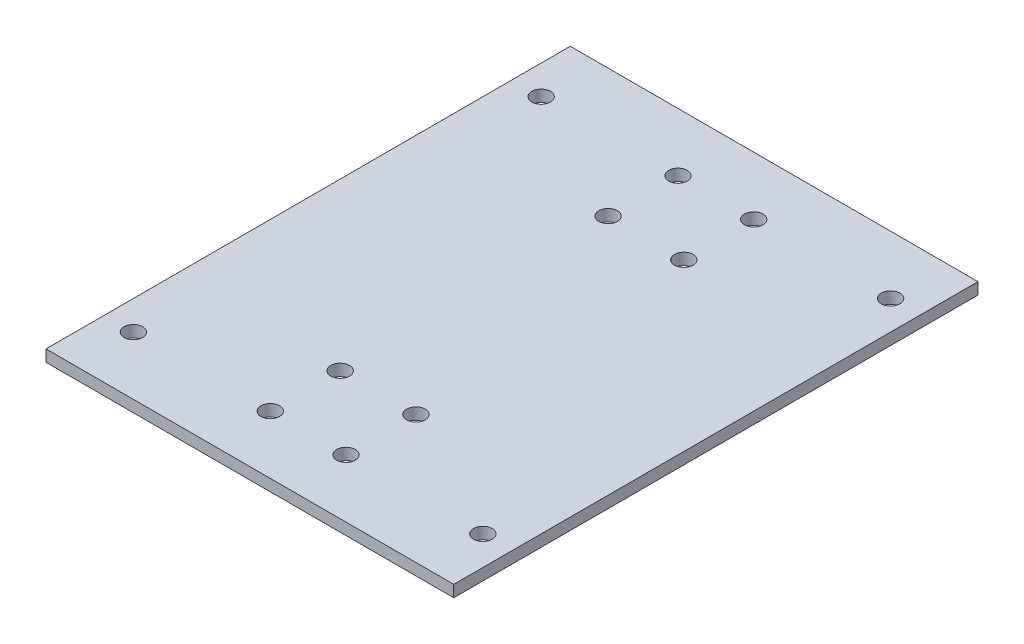
SolidWorks part; units mm, degrees
ref_plane "前基準面" through (0, 0, 0) normal (0, 0, 1) x (1, 0, 0)
ref_plane "上基準面" through (0, 0, 0) normal (0, 1, 0) x (1, 0, 0)
ref_plane "右基準面" through (0, 0, 0) normal (1, 0, 0) x (0, 0, -1)
sketch "草圖2" plane through (0, 0, 0) normal (0, 1, 0) x (1, 0, 0)
  line L1 (-35, -45) -> (35, -45)
  line L2 (-35, -45) -> (-35, 45)
  line L3 (-35, 45) -> (35, 45)
  line L4 (35, -45) -> (35, 45)
  line L5 (0, 45) -> (0, -45) construction
  line L6 (-35, 0) -> (35, 0) construction
  circle A0 centre (-6.5, 35) radius 1.6
  circle A1 centre (-6.5, -35) radius 1.6
  circle A2 centre (-6.5, 23) radius 1.6
  circle A3 centre (-6.5, -23) radius 1.6
  circle A4 centre (6.5, -35) radius 1.6
  circle A5 centre (6.5, -23) radius 1.6
  circle A6 centre (6.5, 23) radius 1.6
  circle A7 centre (6.5, 35) radius 1.6
  circle A8 centre (-30, 35) radius 1.6
  circle A9 centre (30, 35) radius 1.6
  circle A10 centre (-30, -35) radius 1.6
  circle A11 centre (30, -35) radius 1.6
  point P0 (0, 0)
  dimension "D4" = 3.2
  dimension "D9" = 3.2
  dimension "D1" = 90
  dimension "D2" = 70
  dimension "D3" = 58
  dimension "D5" = 13
  dimension "D6" = 12
  dimension "D7" = 70
  dimension "D8" = 60
extrude "填料-伸長1" add sketch "草圖2" along normal blind 2
